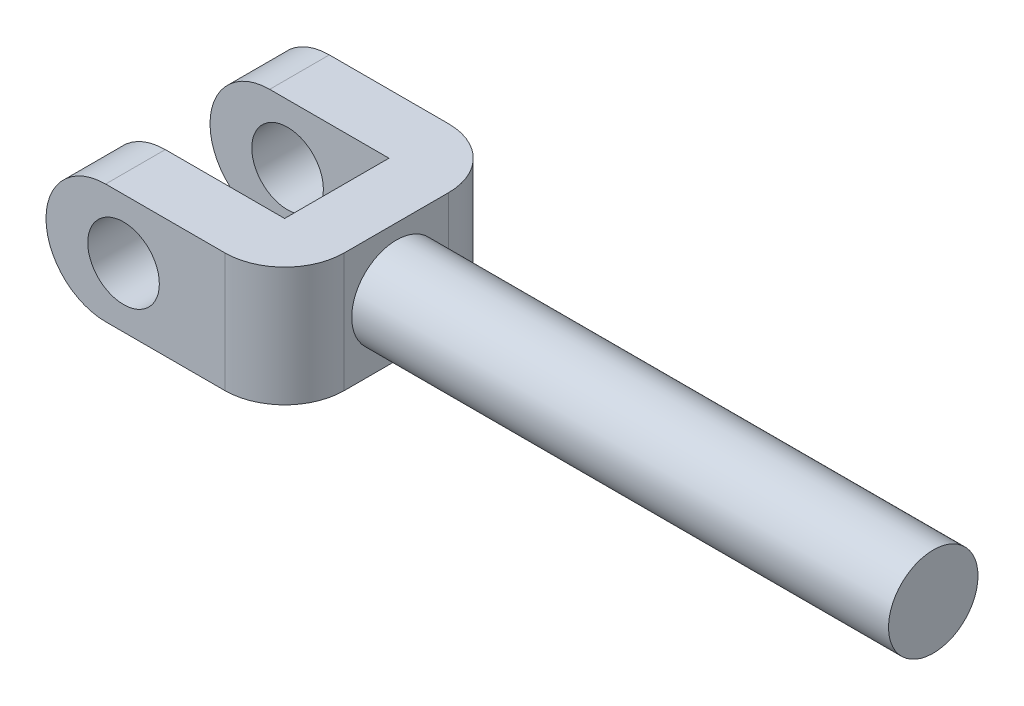
SolidWorks part; units mm, degrees
ref_plane "Front Plane" through (0, 0, 0) normal (0, 0, 1) x (1, 0, 0)
ref_plane "Top Plane" through (0, 0, 0) normal (0, 1, 0) x (1, 0, 0)
ref_plane "Right Plane" through (0, 0, 0) normal (1, 0, 0) x (0, 0, -1)
sketch "Sketch1" plane through (0, 0, 0) normal (1, 0, 0) x (0, 0, -1)
  circle A0 centre (0, 0) radius 0.75
  dimension "D1" = 1.5
extrude "Boss-Extrude1" add sketch "Sketch1" along normal blind 10
sketch "Sketch2" plane through (0, 0, 0) normal (0, 1, 0) x (1, 0, 0)
  line L0 (1, 1.875) -> (1, -1.875)
  line L2 (0, 0.875) -> (0, -0.875)
  line L5 (1, -1.875) -> (-3, -1.875)
  line L6 (-3, 1.875) -> (-3, 0.875)
  line L7 (1, 1.875) -> (-3, 1.875)
  line L8 (0, 0.875) -> (-3, 0.875)
  line L10 (-3, -0.875) -> (0, -0.875)
  line L11 (-3, -0.875) -> (-3, -1.875)
  point P1 (0, 0)
  dimension "D1" = 4
  dimension "D2" = 0
extrude "Boss-Extrude2" add sketch "Sketch2" along normal blind 1 and the other way blind 1
fillet "Fillet1" radius 1 6 edges at (-3, 1, -1.375) (-3, -1, -1.375) (-3, -1, 1.375) (-3, 1, 1.375) (1, 0, -1.875) (1, 0, 1.875)
sketch "Sketch3" plane through (0, 0, -1.875) normal (0, 0, -1) x (-1, 0, 0)
  line L0 (0, -1) -> (2, -1) construction
  line L2 (0, 1) -> (0, -1) construction
  circle A0 centre (1.7, 0) radius 0.6
  dimension "D1" = 1.2
  dimension "D2" = 1
  dimension "D3" = 1.7
extrude "Cut-Extrude1" cut sketch "Sketch3" against normal blind 5
